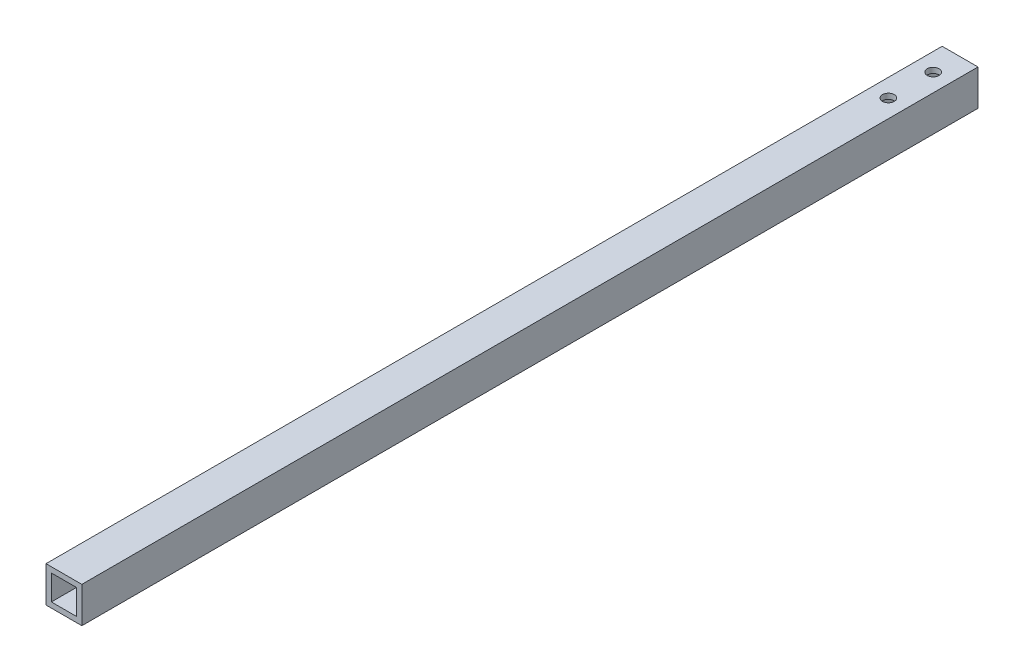
SolidWorks part; units mm, degrees
material "PC 高粘度"
ref_plane "前视基准面" through (0, 0, 0) normal (0, 0, 1) x (1, 0, 0)
ref_plane "上视基准面" through (0, 0, 0) normal (0, 1, 0) x (1, 0, 0)
ref_plane "右视基准面" through (0, 0, 0) normal (1, 0, 0) x (0, 0, -1)
other "Configuration Table"
sketch "草图1" plane through (0, 0, 0) normal (0, 0, 1) x (1, 0, 0)
  line L0 (-3.5, 3.5) -> (-3.5, -3.5)
  line L1 (-5, 5) -> (5, 5)
  line L2 (-5, 5) -> (-5, -5)
  line L3 (-5, -5) -> (5, -5)
  line L4 (5, 5) -> (5, -5)
  line L5 (0, -5) -> (0, 5) construction
  line L6 (-5, 0) -> (5, 0) construction
  line L7 (-3.5, -3.5) -> (3.5, -3.5)
  line L8 (3.5, 3.5) -> (3.5, -3.5)
  line L9 (-3.5, 3.5) -> (3.5, 3.5)
  point P0 (0, 0)
  dimension "D1" = 10
  dimension "D2" = 1.5
extrude "凸台-拉伸1" add sketch "草图1" along normal blind 250
sketch "草图2" plane through (0, 5, 0) normal (0, 1, 0) x (1, 0, 0)
  circle A0 centre (0, -7.5) radius 1.65 construction
  circle A1 centre (0, -20) radius 1.65 construction
  circle A2 centre (0, -7.5) radius 1.65
  circle A3 centre (0, -20) radius 1.65
extrude "切除-拉伸1" cut sketch "草图2" against normal through all
